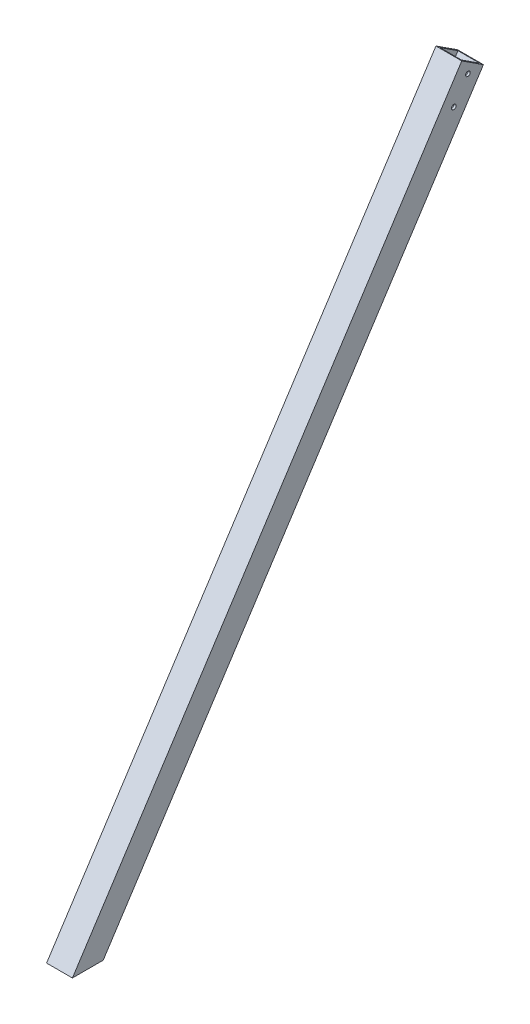
SolidWorks part; units mm, degrees
material "6063-T6"
ref_plane "Front Plane" through (0, 0, 0) normal (0, 0, 1) x (1, 0, 0)
ref_plane "Top Plane" through (0, 0, 0) normal (0, 1, 0) x (1, 0, 0)
ref_plane "Right Plane" through (0, 0, 0) normal (1, 0, 0) x (0, 0, -1)
sketch "Sketch1" plane through (0, 0, 0) normal (1, 0, 0) x (0, 0, -1)
  line L0 (-407.3116, 50.8) -> (196.85, 981.1273)
  line L1 (196.85, 981.1273) -> (196.85, 911.1727)
  line L2 (196.85, 911.1727) -> (-361.8826, 50.8)
  line L3 (-361.8826, 50.8) -> (-407.3116, 50.8)
  line L5 (203.2, 927.1) -> (241.3, 927.1) construction
  line L6 (203.2, 927.1) -> (203.2, 965.2) construction
  line L7 (203.2, 965.2) -> (241.3, 965.2) construction
  line L8 (241.3, 927.1) -> (241.3, 965.2) construction
  line L9 (0, 0) -> (-6.35, 0) construction
  line L10 (0, 0) -> (0, 482.6) construction
  line L11 (0, 482.6) -> (-6.35, 482.6) construction
  line L12 (-6.35, 0) -> (-6.35, 482.6) construction
  circle A0 centre (-33.782, 486.664) radius 21.082 construction
  point P2 (203.2, 946.15)
  point P7 (196.85, 946.15)
  dimension "D8" = 6.35
  dimension "D10" = 42.164
  dimension "D11" = 16.6977
  dimension "D1" = 38.1
  dimension "D2" = 50.8
  dimension "D3" = 38.1
  dimension "D4" = 927.1
  dimension "D5" = 203.2
  dimension "D6" = 6.35
  dimension "D7" = 482.6
  dimension "D9" = 486.664
  dimension "D12" = 57
  dimension "D13" = 407.3116
  dimension "D14" = 6.35
extrude "Boss-Extrude1" add sketch "Sketch1" along normal blind 38.1
shell "Shell1" thickness 3.175 removed face at (19.05, 50.8, 384.5971) removed face at (19.05, 946.15, -196.85)
hole_wizard "1/4 Clearance Hole1" positions "Sketch2" profile "Sketch3" hole size "1/4" standard "ANSI Inch" end condition through all
sketch "Sketch2" plane through (38.1, 0, 0) normal (1, 0, 0) x (0, 0, -1)
  line L0 (196.85, 946.15) -> (-384.5971, 50.8) construction
  line L1 (196.85, 911.1727) -> (196.85, 981.1273) construction
  line L2 (-407.3116, 50.8) -> (-361.8826, 50.8) construction
  point P0 (176.0993, 914.1967)
  point P2 (155.3485, 882.2433)
  dimension "D1" = 38.1
  dimension "D2" = 38.1
sketch "Sketch3" plane through (38.1, 914.1967, -176.0993) normal (0, 1, 0) x (0, 0, -1)
  line L0 (0, 0) -> (0, 38.1)
  line L1 (0, 38.1) -> (3.3782, 38.1)
  line L2 (3.3782, 38.1) -> (3.3782, 0)
  line L5 (3.3782, 0) -> (0, 0)
  line L11 (0, -6.35) -> (0, 107.95) construction
  dimension "Thru Hole Dia." = 6.7564
  dimension "Thru Hole Depth" = 38.1
sketch "Sketch5" plane through (38.1, 0, 0) normal (1, 0, 0) x (0, 0, -1)
  line L0 (202.4513, 919.798) -> (196.85, 923.4355)
  line L2 (202.4513, 919.798) -> (196.85, 911.1727)
  line L3 (-361.8826, 50.8) -> (196.85, 911.1727) construction
  line L4 (196.85, 911.1727) -> (196.85, 981.1273) construction
  line L5 (196.85, 911.1727) -> (196.85, 923.4355)
  point P9 (176.0993, 914.1967)
  dimension "D1" = 19.05
  dimension "D2" = 10.2844
extrude "Boss-Extrude2" [suppressed] add sketch "Sketch5" against normal blind 38.1
sketch "Sketch6" [suppressed] plane through (38.1, 0, 0) normal (1, 0, 0) x (0, 0, -1)
  line L0 (202.4513, 919.798) -> (170.498, 940.5487)
  line L1 (196.85, 981.1273) -> (-407.3116, 50.8) construction
  line L2 (170.498, 940.5487) -> (196.85, 981.1273)
  line L3 (196.85, 981.1273) -> (228.8033, 960.3765)
  line L4 (228.8033, 960.3765) -> (202.4513, 919.798)
extrude "Cut-Extrude1" [suppressed] cut sketch "Sketch6" against normal through all
sketch "Sketch7" plane through (38.1, 0, 0) normal (1, 0, 0) x (0, 0, -1)
  line L6 (196.85, 911.1727) -> (198.9928, 914.4724)
  line L7 (198.9928, 914.4724) -> (196.85, 915.864)
  line L8 (196.85, 911.1727) -> (196.85, 981.1273) construction
  line L9 (196.85, 915.864) -> (196.85, 911.1727)
  line L10 (-361.8826, 50.8) -> (196.85, 911.1727) construction
  circle A1 centre (176.0993, 914.1967) radius 3.3782 construction
  dimension "D1" = 12.7
extrude "Boss-Extrude3" add sketch "Sketch7" against normal up to surface (38.1 mm away) up to face at (0, 914.1967, -179.4775)
sketch "Sketch8" plane through (38.1, 0, 0) normal (1, 0, 0) x (0, 0, -1)
  line L0 (196.85, 915.864) -> (167.0395, 935.2231)
  line L1 (196.85, 981.1273) -> (-407.3116, 50.8) construction
  line L2 (198.9928, 914.4724) -> (196.85, 915.864) construction
  line L3 (167.0395, 935.2231) -> (196.85, 981.1273)
  line L4 (196.85, 981.1273) -> (196.85, 915.864)
extrude "Cut-Extrude2" cut sketch "Sketch8" against normal through all
